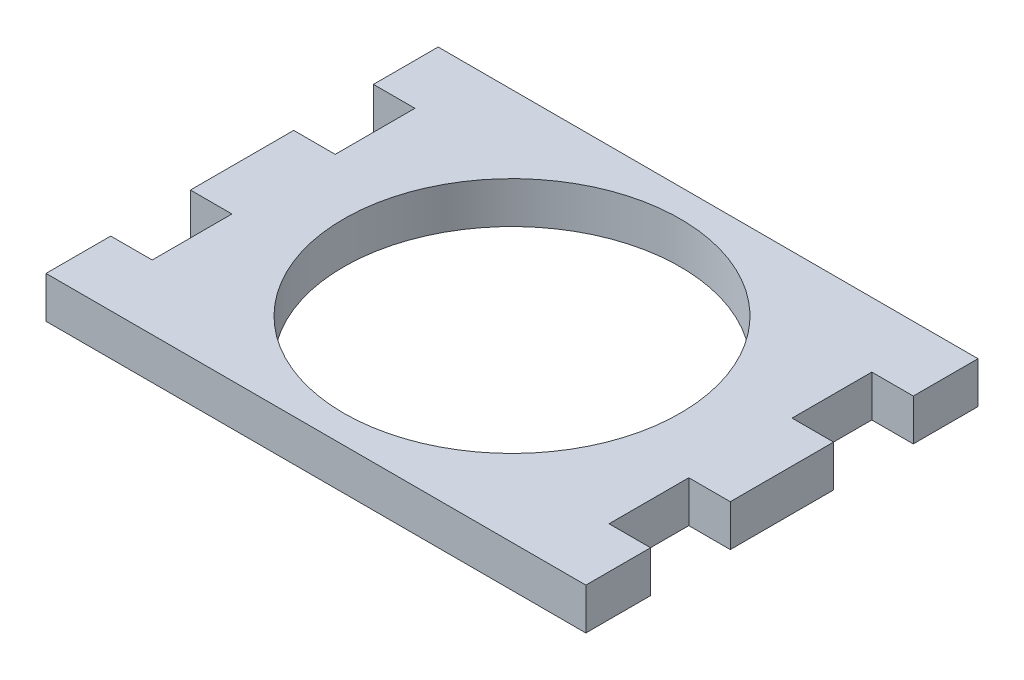
SolidWorks part; units mm, degrees
ref_plane "Front Plane" through (0, 0, 0) normal (0, 0, 1) x (1, 0, 0)
ref_plane "Top Plane" through (0, 0, 0) normal (0, 1, 0) x (1, 0, 0)
ref_plane "Right Plane" through (0, 0, 0) normal (1, 0, 0) x (0, 0, -1)
sketch "Sketch1" plane through (0, 0, 0) normal (0, 1, 0) x (1, 0, 0)
  line L0 (-20.65, 0) -> (0, 0) construction
  line L1 (-20.65, 15) -> (20.65, 15)
  line L2 (-20.65, 15) -> (-20.65, 10.05)
  line L3 (-20.65, -15) -> (20.65, -15)
  line L5 (0, 15) -> (0, -15) construction
  line L6 (20.65, -10.05) -> (20.65, -15)
  line L7 (20.65, -10.05) -> (17.475, -10.05)
  line L8 (-20.65, -10.05) -> (-17.475, -10.05)
  line L9 (-17.475, -10.05) -> (-17.475, -3.95)
  line L10 (-17.475, -3.95) -> (-20.65, -3.95)
  line L11 (-20.65, 3.95) -> (-20.65, -3.95)
  line L12 (-20.65, -10.05) -> (-20.65, -15)
  line L13 (-20.65, 10.05) -> (-17.475, 10.05)
  line L14 (-17.475, 10.05) -> (-17.475, 3.95)
  line L15 (-17.475, 3.95) -> (-20.65, 3.95)
  line L16 (17.475, -10.05) -> (17.475, -3.95)
  line L17 (17.475, -3.95) -> (20.65, -3.95)
  line L18 (20.65, 3.95) -> (20.65, -3.95)
  line L19 (17.475, 3.95) -> (20.65, 3.95)
  line L20 (17.475, 10.05) -> (17.475, 3.95)
  line L21 (20.65, 10.05) -> (17.475, 10.05)
  line L22 (20.65, 15) -> (20.65, 10.05)
  circle A0 centre (0, 0) radius 12.875
  dimension "D1" = 25.75
  dimension "D2" = 3.175
  dimension "D3" = 7.9
  dimension "D4" = 6.1
  dimension "D5" = 20.65
  dimension "D6" = 30
extrude "Boss-Extrude1" add sketch "Sketch1" along normal blind 3.175
